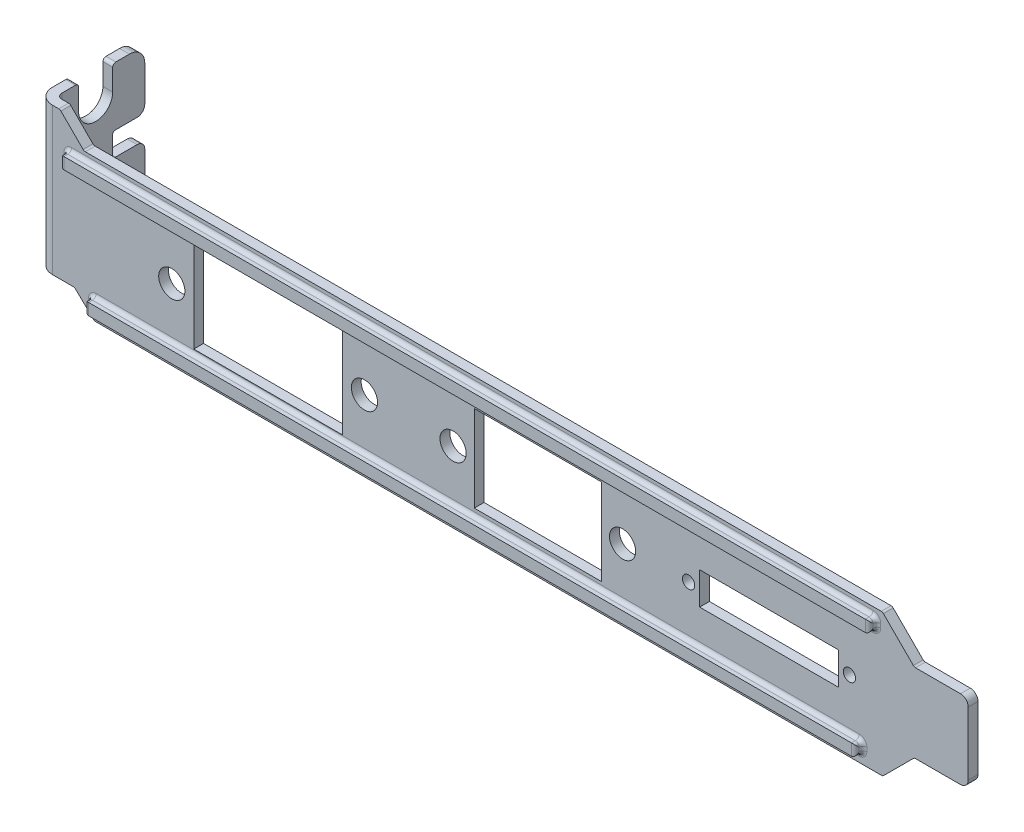
SolidWorks part; units mm, degrees
ref_plane "Front Plane" through (0, 0, 0) normal (0, 0, 1) x (1, 0, 0)
ref_plane "Top Plane" through (0, 0, 0) normal (0, 1, 0) x (1, 0, 0)
ref_plane "Right Plane" through (0, 0, 0) normal (1, 0, 0) x (0, 0, -1)
sketch "Sketch1" plane through (0, 0, 0) normal (0, 0, 1) x (1, 0, 0)
  line L0 (0, 2.48) -> (4.88, 2.48)
  line L5 (7.45, 0) -> (109.76, 0)
  line L6 (0, 2.48) -> (0, 21.53)
  line L7 (6.11, 18.42) -> (109.73, 18.42)
  line L8 (113.85, 4.09) -> (113.85, 14.3) construction
  line L9 (4.88, 2.48) -> (7.45, 0)
  line L10 (109.76, 0) -> (113.85, 4.09)
  line L11 (109.73, 18.42) -> (113.85, 14.3)
  line L12 (6.11, 18.42) -> (3, 21.53)
  line L13 (3, 21.53) -> (0, 21.53)
  line L16 (113.85, 14.3) -> (120.85, 14.3)
  line L18 (113.85, 4.09) -> (120.85, 4.09)
  line L19 (120.85, 14.3) -> (120.85, 4.09)
  dimension "D1" = 7.45
  dimension "D2" = 2.48
  dimension "D3" = 4.88
  dimension "D4" = 106.4
  dimension "D5" = 135
  dimension "D6" = 4.09
  dimension "D7" = 10.21
  dimension "D8" = 135
  dimension "D9" = 18.42
  dimension "D10" = 19.05
  dimension "D11" = 135
  dimension "D12" = 3
  dimension "D13" = 7
extrude "Boss-Extrude1" add sketch "Sketch1" along normal blind 1.27
sketch "Sketch8" plane through (0, 0, 0) normal (0, 0, -1) x (-1, 0, 0)
  line L0 (0, 2.48) -> (-4.88, 2.48) construction
  line L1 (0, 21.53) -> (-1.27, 21.53)
  line L2 (0, 21.53) -> (0, 2.48)
  line L3 (0, 2.48) -> (-1.27, 2.48)
  line L4 (-1.27, 21.53) -> (-1.27, 2.48)
  dimension "D1" = 1.27
extrude "Boss-Extrude3" add sketch "Sketch8" along normal blind 11.454
sketch "Sketch9" plane through (0, 0, 0) normal (-1, 0, 0) x (0, 0, 1)
  line L0 (1.27, 21.53) -> (1.27, 2.48) construction
  line L1 (-7.29, 18.35) -> (-7.29, 21.53)
  line L2 (1.27, 21.53) -> (-11.454, 21.53) construction
  line L3 (-7.29, 21.53) -> (-2.87, 21.53)
  line L4 (-2.87, 21.53) -> (-2.87, 18.35)
  line L5 (-11.454, 2.48) -> (-11.454, 21.53) construction
  line L6 (-11.454, 13.91) -> (-7.264, 13.91)
  line L7 (-11.454, 13.91) -> (-11.454, 10.86)
  line L8 (-11.454, 10.86) -> (-7.264, 10.86)
  line L9 (-7.264, 13.91) -> (-7.264, 10.86)
  arc A0 (-7.29, 18.35) -> (-2.87, 18.35) centre (-5.08, 18.35) ccw
  dimension "D3" = 2.21
  dimension "D1" = 6.35
  dimension "D2" = 3.18
  dimension "D4" = 4.19
  dimension "D5" = 3.05
  dimension "D6" = 7.62
extrude "Cut-Extrude6" cut sketch "Sketch9" against normal up to next
ref_plane "Plane1" through (0, 9.21, 0) normal (0, -1, 0) x (-1, 0, 0)
sketch "Sketch10" plane through (0, 0, 1.27) normal (0, 0, -1) x (-1, 0, 0)
  line L1 (-7.2, 1.2) -> (-107.2, 1.2)
  line L2 (-7.2, 1.2) -> (-7.2, 2.7)
  line L3 (-7.2, 2.7) -> (-107.2, 2.7)
  line L4 (-107.2, 1.2) -> (-107.2, 2.7)
  line L5 (-109, 16) -> (-4, 16)
  line L6 (-109, 16) -> (-109, 17.5)
  line L7 (-109, 17.5) -> (-4, 17.5)
  line L8 (-4, 16) -> (-4, 17.5)
  dimension "D1" = 1.5
  dimension "D2" = 1.2
  dimension "D3" = 7.2
  dimension "D4" = 100
  dimension "D5" = 4
  dimension "D6" = 16
  dimension "D7" = 105
extrude "Boss-Extrude4" add sketch "Sketch10" against normal blind 1
sketch "Sketch3" plane through (0, 0, 1.27) normal (0, 0, 1) x (1, 0, 0)
  line L1 (17.5, 9.21) -> (42.5, 9.21) construction
  line L2 (20.35, 3.285) -> (39.65, 3.285)
  line L3 (20.35, 3.285) -> (20.35, 15.135)
  line L4 (20.35, 15.135) -> (39.65, 15.135)
  line L5 (39.65, 3.285) -> (39.65, 15.135)
  line L6 (20.35, 3.285) -> (39.65, 15.135) construction
  line L7 (20.35, 15.135) -> (39.65, 3.285) construction
  line L8 (0, 21.53) -> (0, 2.48) construction
  line L9 (-0.6985, 9.21) -> (0.6985, 9.21) construction
  circle A0 centre (17.5, 9.21) radius 1.7
  circle A1 centre (42.5, 9.21) radius 1.7
  point P4 (30, 9.21)
  point P8 (30, 9.21)
  dimension "D2" = 3.4
  dimension "D3" = 25
  dimension "D1" = 30
  dimension "D4" = 11.85
  dimension "D5" = 19.3
extrude "XT60 cutout" cut sketch "Sketch3" against normal through all
sketch "Sketch5" plane through (0, 0, 1.27) normal (0, 0, 1) x (1, 0, 0)
  line L0 (-0.6985, 9.21) -> (0.6985, 9.21) construction
  line L1 (54, 9.21) -> (76, 9.21) construction
  line L2 (56.75, 3.61) -> (73.25, 3.61)
  line L3 (56.75, 3.61) -> (56.75, 14.81)
  line L4 (56.75, 14.81) -> (73.25, 14.81)
  line L5 (73.25, 3.61) -> (73.25, 14.81)
  line L6 (56.75, 3.61) -> (73.25, 14.81) construction
  line L7 (56.75, 14.81) -> (73.25, 3.61) construction
  circle A0 centre (54, 9.21) radius 1.7
  circle A1 centre (76, 9.21) radius 1.7
  point P4 (65, 9.21)
  point P8 (65, 9.21)
  dimension "D2" = 3.4
  dimension "D3" = 22
  dimension "D1" = 65
  dimension "D4" = 11.2
  dimension "D5" = 16.5
extrude "Cut-Extrude4" cut sketch "Sketch5" against normal through all and the other way through all
sketch "Sketch6" plane through (0, 0, 1.27) normal (0, 0, 1) x (1, 0, 0)
  line L0 (84.56, 9.21) -> (105.44, 9.21) construction
  line L1 (86, 7.11) -> (104, 7.11)
  line L2 (86, 7.11) -> (86, 11.31)
  line L3 (86, 11.31) -> (104, 11.31)
  line L4 (104, 7.11) -> (104, 11.31)
  line L5 (86, 7.11) -> (104, 11.31) construction
  line L6 (86, 11.31) -> (104, 7.11) construction
  line L7 (-0.6985, 9.21) -> (0.6985, 9.21) construction
  circle A0 centre (105.44, 9.21) radius 0.8
  circle A1 centre (84.56, 9.21) radius 0.8
  point P0 (95, 9.21)
  point P12 (95, 9.21)
  dimension "D4" = 1.6
  dimension "D1" = 18
  dimension "D2" = 4.2
  dimension "D3" = 95
  dimension "D5" = 20.88
extrude "Cut-Extrude5" cut sketch "Sketch6" against normal through all
fillet "Fillet1" radius 0.4 12 edges at (109.76, 0, 0.635) (113.85, 4.09, 0.635) (113.85, 14.3, 0.635) (109.73, 18.42, 0.635) (4.88, 2.48, 0.635) (7.45, 0, 0.635) (3, 21.53, 0.635) (6.11, 18.42, 0.635) (0.635, 21.53, -7.29) (0.635, 21.53, -2.87) (0.635, 10.86, -7.264) (0.635, 13.91, -7.264)
fillet "Fillet2" radius 1 4 edges at (0.635, 13.91, -11.454) (0.635, 10.86, -11.454) (120.85, 14.3, 0.635) (120.85, 4.09, 0.635)
fillet "Fillet3" radius 2 3 edges at (0, 12.005, 1.27) (0.635, 2.48, -11.454) (0.635, 21.53, -11.454)
fillet "Fillet4" radius 0.5 20 edges at (109, 17.5, 1.77) (109, 16.75, 2.27) (109, 16, 1.77) (107.2, 2.7, 1.77) (107.2, 1.95, 2.27) (107.2, 1.2, 1.77) (4, 16, 1.77) (4, 16.75, 2.27) (4, 17.5, 1.77) (7.2, 1.2, 1.77) (7.2, 1.95, 2.27) (7.2, 2.7, 1.77) (56.5, 17.5, 1.27) (56.5, 16, 1.27) (57.2, 2.7, 1.27) (57.2, 1.2, 1.27) (109, 16.75, 1.27) (107.2, 1.95, 1.27) (4, 16.75, 1.27) (7.2, 1.95, 1.27)
fillet "Fillet5" radius 0.7 1 edges at (1.27, 12.005, 0)
